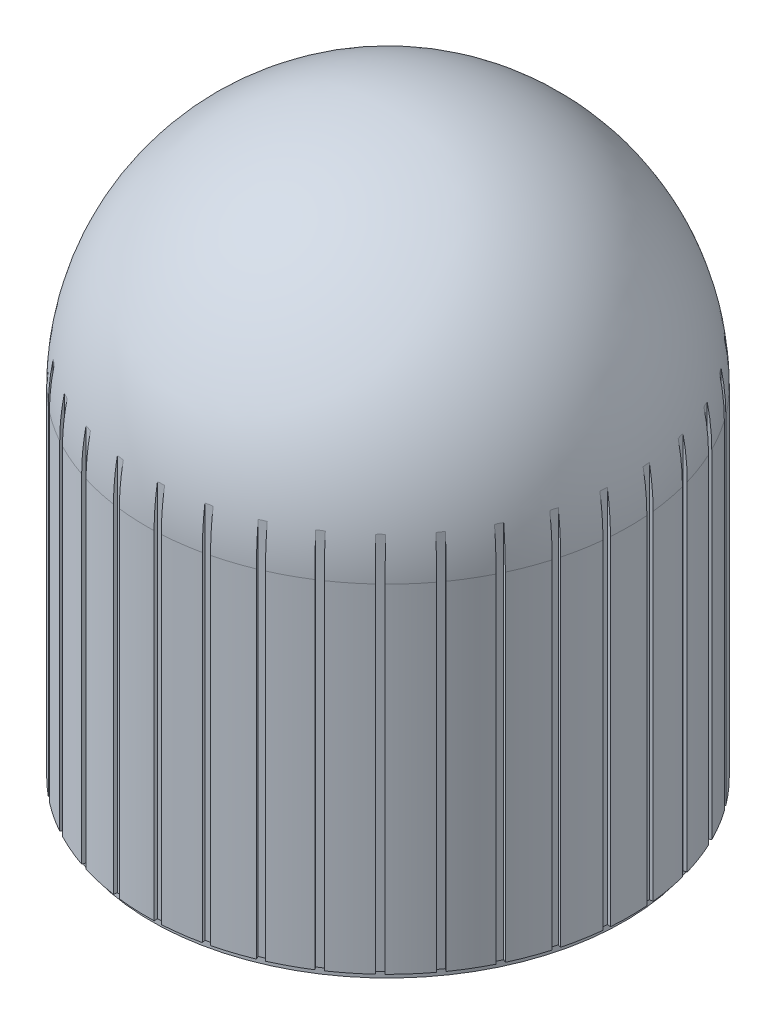
SolidWorks part; units mm, degrees
ref_plane "前视基准面" through (0, 0, 0) normal (0, 0, 1) x (1, 0, 0)
ref_plane "上视基准面" through (0, 0, 0) normal (0, 1, 0) x (1, 0, 0)
ref_plane "右视基准面" through (0, 0, 0) normal (1, 0, 0) x (0, 0, -1)
other "Configuration Table"
sketch "草图1" plane through (0, 0, 0) normal (0, 1, 0) x (1, 0, 0)
  line L0 (-3, 0) -> (3, 0) construction
  line L1 (-2.5981, 1.5) -> (2.5981, 1.5) construction
  line L2 (-2.5981, 1.5) -> (2.5981, 1.5)
  arc A0 (-2.5981, 1.5) -> (2.5981, 1.5) centre (0, 0) ccw
  circle A1 centre (0, 0) radius 7
  dimension "D1" = 6
  dimension "D3" = 14
  dimension "D2" = 1.5
extrude "凸台-拉伸1" add sketch "草图1" along normal blind 10
sketch "草图2" plane through (0, 0, 0) normal (0, -1, 0) x (1, 0, 0)
  circle A0 centre (0, 0) radius 3
  dimension "D1" = 6
extrude "切除-拉伸1" cut sketch "草图2" against normal blind 4
sketch "草图3" plane through (0, 10, 0) normal (0, 1, 0) x (1, 0, 0)
  line L0 (0, 7) -> (0, -7)
  arc A0 (0, 7) -> (0, -7) centre (0, 0) ccw
  dimension "D1" = 14
revolve "旋转1" add sketch "草图3" angle 180 about L0 reverse direction yes
sketch "草图4" plane through (0, 0, 0) normal (0, -1, 0) x (1, 0, 0)
  line L0 (0, 0) -> (-7, 0) construction
  line L1 (-6.9993, 0.1) -> (-6.8993, 0.1)
  line L2 (-6.8993, 0.1) -> (-6.8993, -0.1)
  line L3 (-6.8993, -0.1) -> (-6.9993, -0.1)
  circle A0 centre (0, 0) radius 7
  circle M6 centre (0, 0) radius 7
  dimension "D3" = 14
  dimension "D1" = 0.2
  dimension "D2" = 0.1
extrude "切除-拉伸2" cut sketch "草图4" against normal through all contours L2 L0 A0 L3 | L0 L2 L1 M6 region at (-6.9495, 0, -0.0499) region at (-6.9495, 0, 0.0499)
ref_axis "基准轴1" through (0, 3.6754, 0) along (0, -1, 0)
pattern_circular "阵列(圆周)1" count 35 over 360 about axis through (0, 3.6754, 0) along (0, -1, 0) of "切除-拉伸2"
sketch "草图5" plane through (0, 0, 0) normal (0, -1, 0) x (1, 0, 0)
  circle A0 centre (0, 0) radius 6.85
  circle A1 centre (0, 0) radius 7.2176
  dimension "D1" = 13.7
extrude "切除-拉伸3" cut sketch "草图5" against normal blind 0.2
equation "\"0。5\"=0.441986"
